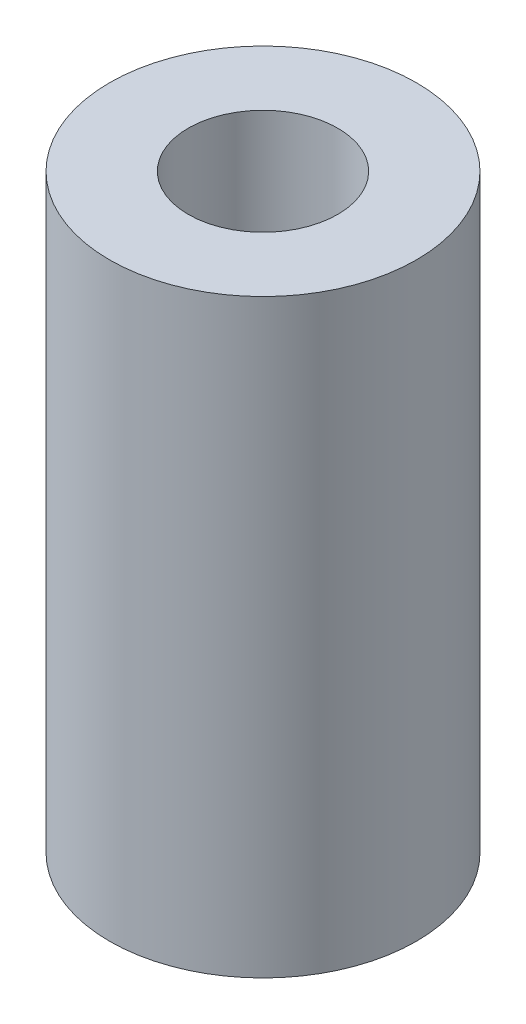
SolidWorks part; units mm, degrees
ref_plane "Front Plane" through (0, 0, 0) normal (0, 0, 1) x (1, 0, 0)
ref_plane "Top Plane" through (0, 0, 0) normal (0, 1, 0) x (1, 0, 0)
ref_plane "Right Plane" through (0, 0, 0) normal (1, 0, 0) x (0, 0, -1)
sketch "Sketch1" plane through (0, 0, 0) normal (0, 1, 0) x (1, 0, 0)
  circle A0 centre (0, 0) radius 1.9
  circle A1 centre (0, 0) radius 3.9
  dimension "D1" = 3.8
  dimension "D2" = 2
extrude "Boss-Extrude1" add sketch "Sketch1" along normal blind 15
